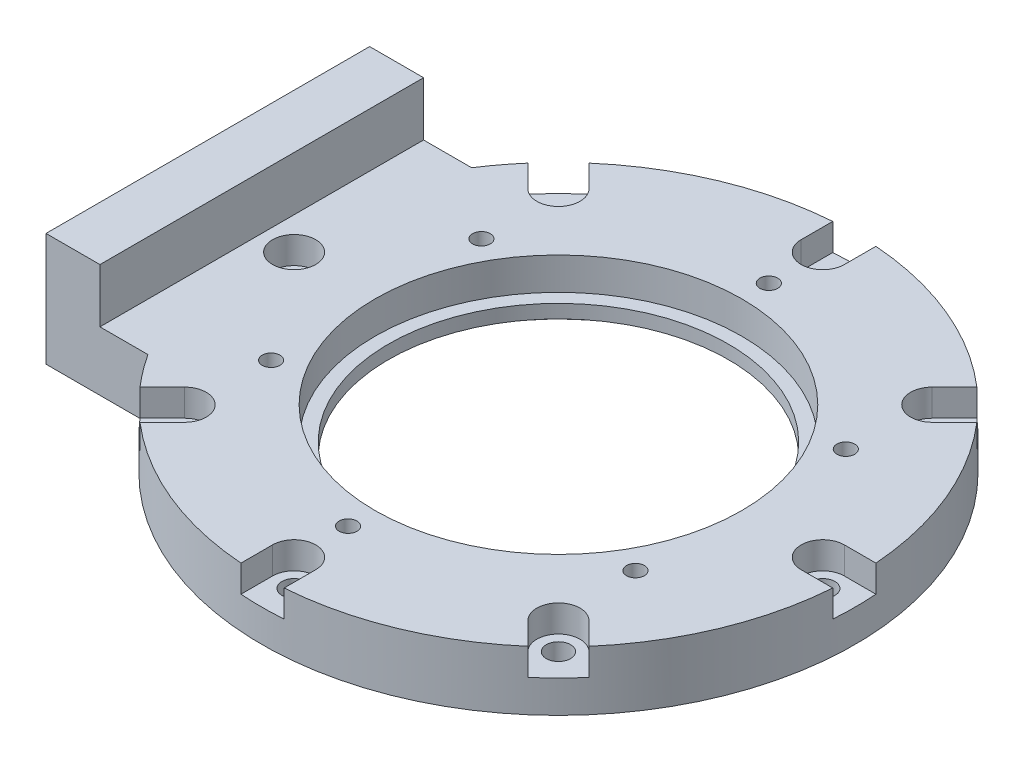
SolidWorks part; units mm, degrees
material "7075-T6, 플레이트 (SS)"
ref_plane "정면" through (0, 0, 0) normal (0, 0, 1) x (1, 0, 0)
ref_plane "윗면" through (0, 0, 0) normal (0, 1, 0) x (1, 0, 0)
ref_plane "우측면" through (0, 0, 0) normal (1, 0, 0) x (0, 0, -1)
sketch "스케치1" plane through (0, 0, 0) normal (0, 1, 0) x (1, 0, 0)
  line L1 (0, -55) -> (-65, -55)
  line L3 (0, 55) -> (-65, 55)
  line L4 (-65, -55) -> (-65, 55)
  line L5 (65, -55) -> (-65, 55) construction
  line L6 (65, 55) -> (-65, -55) construction
  arc A0 (0, -55) -> (0, 55) centre (0, 0) ccw
  circle A2 centre (0, 0) radius 35
  dimension "D1" = 110
  dimension "D4" = 70
  dimension "D2" = 110
  dimension "D3" = 130
extrude "보스-돌출1" add sketch "스케치1" along normal blind 2.5
sketch "스케치2" plane through (0, 2.5, 0) normal (0, 1, 0) x (1, 0, 0)
  line L0 (-65, 55) -> (-65, -55) construction
  line L1 (-65, -55) -> (0, -55) construction
  line L2 (0, 55) -> (-65, 55) construction
  line L3 (-65, 55) -> (-65, -55)
  line L4 (-65, -55) -> (0, -55)
  line L5 (0, 55) -> (-65, 55)
  circle A0 centre (0, 0) radius 31.5
  arc A1 (0, -55) -> (0, 55) centre (0, 0) ccw construction
  arc A2 (0, -55) -> (0, 55) centre (0, 0) ccw
  dimension "D1" = 63
extrude "보스-돌출2" add sketch "스케치2" along normal blind 2.5
sketch "스케치3" plane through (0, 5, 0) normal (0, 1, 0) x (1, 0, 0)
  line L0 (-65, 55) -> (-65, -55) construction
  line L1 (-65, -55) -> (0, -55) construction
  line L2 (0, 55) -> (-65, 55) construction
  line L3 (-65, 55) -> (-65, -55)
  line L4 (-65, -55) -> (0, -55)
  line L5 (0, 55) -> (-65, 55)
  circle A0 centre (0, 0) radius 34
  arc A1 (0, -55) -> (0, 55) centre (0, 0) ccw construction
  arc A2 (0, -55) -> (0, 55) centre (0, 0) ccw
  dimension "D1" = 68
extrude "보스-돌출3" add sketch "스케치3" along normal blind 6
sketch "스케치5" plane through (0, 11, 0) normal (0, 1, 0) x (1, 0, 0)
  circle A0 centre (0, 0) radius 49 construction
  circle A1 centre (0, 0) radius 39 construction
  point P4 (0, 39)
  point P5 (0, 49)
  dimension "D1" = 98
  dimension "D2" = 78
hole_wizard "M4 육각 소켓 머리 캡 나사용 카운터보어1" positions "스케치6" profile "스케치8" counterbore size "M4" standard "ISO" end condition through all
sketch "스케치6" plane through (0, 11, 0) normal (0, 1, 0) x (1, 0, 0)
  point P0 (0, 49)
sketch "스케치8" plane through (0, 11, -49) normal (1, 0, 0) x (0, 0, 1)
  line L0 (0, 0) -> (0, 11)
  line L1 (0, 11) -> (2.25, 11)
  line L3 (2.25, 11) -> (2.25, 5)
  line L4 (2.25, 5) -> (4, 5)
  line L5 (4, 5) -> (4, 0)
  line L7 (4, 0) -> (0, 0)
  line L11 (0, -6.35) -> (0, 107.95) construction
  dimension "관통 구멍 지름" = 4.5
  dimension "관통 구멍 깊이" = 11
  dimension "카운터보어 지름" = 8
  dimension "카운터보어 깊이" = 5
hole_wizard "M4 탭을 위한 탭 드릴1" positions "스케치9" profile "스케치10" hole size "M4" standard "ISO" end condition through all
sketch "스케치9" plane through (0, 11, 0) normal (0, 1, 0) x (1, 0, 0)
  point P0 (0, 39)
sketch "스케치10" plane through (0, 11, -39) normal (1, 0, 0) x (0, 0, 1)
  line L0 (0, 0) -> (0, 11)
  line L1 (0, 11) -> (1.65, 11)
  line L2 (1.65, 11) -> (1.65, 0)
  line L5 (1.65, 0) -> (0, 0)
  line L11 (0, -6.35) -> (0, 107.95) construction
  dimension "관통 구멍 지름" = 3.3
  dimension "관통 구멍 깊이" = 11
pattern_circular "원형 패턴1" count 8 over 360 about axis through (0, 2.5, 0) along (0, -1, 0) of "M4 육각 소켓 머리 캡 나사용 카운터보어1"
pattern_circular "원형 패턴2" count 6 over 360 about axis through (0, 2.5, 0) along (0, -1, 0) of "M4 탭을 위한 탭 드릴1" reverse direction yes
sketch "스케치11" plane through (0, 11, 0) normal (0, 1, 0) x (1, 0, 0)
  line L1 (4, 61) -> (-4, 61)
  line L2 (4, 61) -> (4, 49)
  line L3 (4, 49) -> (-4, 49)
  line L4 (-4, 61) -> (-4, 49)
  line L5 (4, 61) -> (-4, 49) construction
  line L6 (4, 49) -> (-4, 61) construction
  circle A2 centre (0, 49) radius 4 construction
  circle A3 centre (0, 49) radius 4 construction
  point P0 (0, 55)
extrude "컷-돌출1" cut sketch "스케치11" against normal mid plane 10
sketch "스케치12" plane through (0, 11, 0) normal (0, 1, 0) x (1, 0, 0)
  line L5 (-65, 55) -> (-65, -55) construction
  line L6 (-65, -30) -> (-55, -30)
  line L7 (-65, -30) -> (-65, 30)
  line L8 (-65, 30) -> (-55, 30)
  line L9 (-55, -30) -> (-55, 30)
  line L10 (-65, -55) -> (0, -55) construction
  line L11 (-4, 55) -> (-65, 55) construction
  dimension "D1" = 10
  dimension "D2" = 25
  dimension "D3" = 25
extrude "보스-돌출4" add sketch "스케치12" along normal blind 10
sketch "스케치13" plane through (0, 11, 0) normal (0, 1, 0) x (1, 0, 0)
  line L1 (-65, -30) -> (-46.0977, -30)
  line L2 (-65, -30) -> (-65, 30)
  line L3 (-65, 30) -> (-46.0977, 30)
  line L5 (100, -65) -> (-100, -65)
  line L6 (100, -65) -> (100, 65)
  line L7 (100, 65) -> (-100, 65)
  line L8 (-100, -65) -> (-100, 65)
  line L9 (100, -65) -> (-100, 65) construction
  line L10 (100, 65) -> (-100, -65) construction
  arc A0 (-46.0977, -30) -> (-46.0977, 30) centre (0, 0) ccw
  dimension "D1" = 110
  dimension "D2" = 65
  dimension "D3" = 200
  dimension "D4" = 30
  dimension "D5" = 30
  dimension "D6" = 130
extrude "컷-돌출2" cut sketch "스케치13" against normal through all
pattern_circular "원형 패턴3" count 8 over 360 about axis through (0, 2.5, 0) along (0, -1, 0) skipping 2 of "컷-돌출1" reverse direction yes
